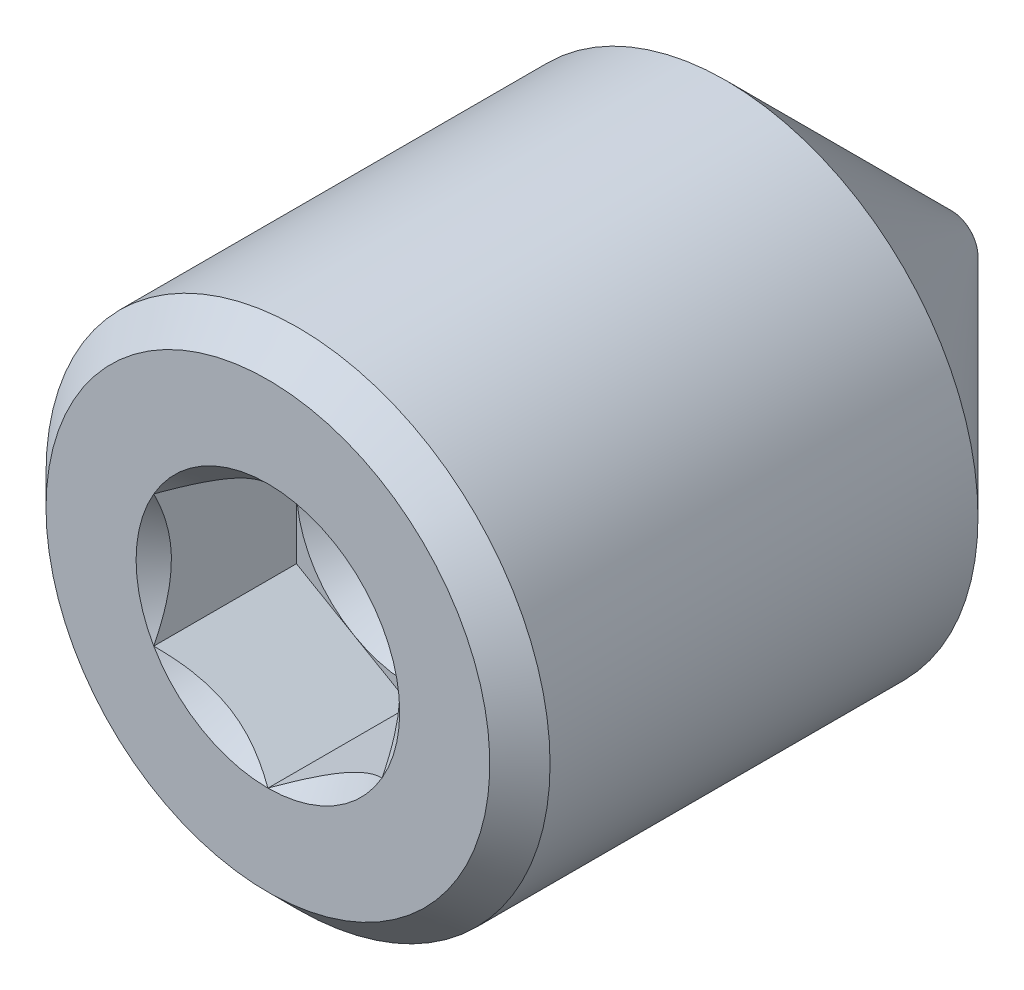
SolidWorks part; units mm, degrees
ref_plane "Front Plane" through (0, 0, 0) normal (0, 0, 1) x (1, 0, 0)
ref_plane "Top Plane" through (0, 0, 0) normal (0, 1, 0) x (1, 0, 0)
ref_plane "Right Plane" through (0, 0, 0) normal (1, 0, 0) x (0, 0, -1)
sketch "Sketch1" plane through (0, 0, 0) normal (1, 0, 0) x (0, 0, -1)
  line L0 (-2.3812, 0) -> (2.3812, 0) construction
  line L5 (-2.3812, 1.7526) -> (-2.3812, -1.7526) construction
  line L6 (2.3812, 0.1753) -> (2.3812, -0.1753) construction
  line L7 (2.3812, 0.1753) -> (0.8039, 1.7526) construction
  line L8 (2.3812, -0.1753) -> (0.8039, -1.7526) construction
  line L9 (-2.9766, 1.8213) -> (-2.3416, 1.8213) construction
  line L10 (-2.3416, 1.8213) -> (-2.6591, 1.2714) construction
  line L11 (-2.6591, 1.2714) -> (-2.9766, 1.8213) construction
  line L12 (-2.9369, 1.7526) -> (-2.3812, 1.7526) construction
  line L13 (-2.6987, 1.3402) -> (-2.6194, 1.3402) construction
  line L14 (-2.6591, 1.3402) -> (-2.6591, 1.2714) construction
  line L15 (-2.6591, 1.7526) -> (-2.6591, 1.8213) construction
  point P24 (-2.3812, 0.7938)
  point P29 (-0.7937, -1.7526)
  dimension "Screw Size Decimal Equivalent" = 3.5052
  dimension "Length" = 4.7625
  dimension "Cone Point Angle" = 90
  dimension "Drive Size" = 1.5875
  dimension "Approx. Point OD" = 0.3505
  dimension "Thread Pitch" = 0.635
  dimension "Pitch/8" = 0.0794
  dimension "Thread Note" = 1.5875
sketch "Sketch2" plane through (0, 0, 0) normal (1, 0, 0) x (0, 0, -1)
  line L0 (-2.3812, 0) -> (2.3812, 0)
  line L1 (2.3812, 0) -> (2.3812, 0.1753)
  line L2 (2.3812, 0.1753) -> (0.8039, 1.7526)
  line L3 (0.8039, 1.7526) -> (-2.3812, 1.7526)
  line L4 (-2.3812, 1.7526) -> (-2.3812, 0)
revolve "Revolve1" add sketch "Sketch2" angle 360 about L0
chamfer "Chamfer1" distance 0.2095 angle 45 1 edges at (1.7526, 0, 2.3812)
sketch "Sketch3" plane through (0, 0, 2.3812) normal (0, 0, 1) x (1, 0, 0)
  line L1 (0, -0.9165) -> (0.7938, -0.4583)
  line L2 (0.7938, -0.4583) -> (0.7938, 0.4583)
  line L3 (0.7938, 0.4583) -> (0, 0.9165)
  line L4 (0, 0.9165) -> (-0.7938, 0.4583)
  line L5 (-0.7938, 0.4583) -> (-0.7938, -0.4583)
  line L6 (-0.7938, -0.4583) -> (0, -0.9165)
  circle A0 centre (0, 0) radius 0.7938 construction
  circle A1 centre (0, 0) radius 1.7526 construction
extrude "Cut-Extrude1" cut sketch "Sketch3" against normal blind 0.9922
sketch "Sketch4" plane through (0, 0, 2.3812) normal (0, 0, 1) x (1, 0, 0)
  circle A0 centre (0, 0) radius 0.9165
extrude "Cut-Extrude2" cut sketch "Sketch4" against normal through all draft 45
sketch "Sketch5" plane through (0, 0, 1.3891) normal (0, 0, 1) x (1, 0, 0)
  line L0 (0, 0.9165) -> (0.7938, 0.4583) construction
  circle A0 centre (0, 0) radius 0.7938
extrude "Cut-Extrude3" cut sketch "Sketch5" against normal through all draft 45
fillet "Fillet1" radius 0.0351 1 edges at (0.1753, 0, -2.3812)
sketch "Sketch6" [suppressed] plane through (0, 0, 2.3812) normal (0, 0, -1) x (-1, 0, 0)
  circle A0 centre (0, 0) radius 1.7526 construction
  circle A1 centre (0, 0) radius 1.7526
sketch "Sketch10" [suppressed] plane through (0, 0, 0) normal (1, 0, 0) x (0, 0, -1)
  line L0 (0.6292, 0) -> (2.371, 0) construction
  line L1 (-2.3812, 0) -> (2.3812, 0) construction
  line L2 (2.371, 0) -> (2.371, 0.1855)
  line L3 (2.371, 0.1855) -> (0.7482, 1.7526)
  line L5 (0.7482, 1.7526) -> (0.6292, 1.7526) construction
  line L6 (0.6292, 1.7526) -> (0.6292, 0) construction
  line L7 (2.371, 0) -> (2.49, 0)
  line L8 (2.49, 0) -> (2.49, 1.7526)
  line L9 (2.49, 1.7526) -> (0.7482, 1.7526)
  dimension "D1" = 44
  dimension "D2" = 0.1191
revolve "Cut-Revolve6" [suppressed] cut sketch "Sketch10" angle 360 about L0
curve "Helix/Spiral1" [suppressed] pitch 0.635 height 5.3975 turns 8.5
sketch "Sketch7" [suppressed] plane through (0, 0, 0) normal (1, 0, 0) x (0, 0, -1)
  line L6 (-2.6987, 1.3402) -> (-2.6194, 1.3402)
  line L9 (-2.6194, 1.3402) -> (-2.3614, 1.787)
  line L10 (-2.3416, 1.8213) -> (-2.6591, 1.2714) construction
  line L11 (-2.3614, 1.787) -> (-2.9567, 1.787)
  line L12 (-2.6591, 1.2714) -> (-2.9766, 1.8213) construction
  line L13 (-2.9567, 1.787) -> (-2.6987, 1.3402)
  line L14 (-2.6591, 1.7526) -> (-2.6591, 1.8213) construction
  point P10 (-2.6591, 1.787)
sweep "Cut-Sweep1" [suppressed] cut profiles "Sketch7" path "Helix/Spiral1"
fillet "Fillet2" [suppressed] radius 0.0351
equation "\"D1@Chamfer1\"=\"Thread Pitch@Sketch1\" * .33"
equation "\"D1@Cut-Extrude1\"=\"Drive Size@Sketch1\"*.625"
equation "\"D4@Helix/Spiral1\"=\"Thread Pitch@Sketch1\""
equation "\"D3@Helix/Spiral1\"=\"Length@Sketch1\"+\"Thread Pitch@Sketch1\""
equation "\"Approx. Point OD@Sketch1\"=\"Screw Size Decimal Equivalent@Sketch1\"*.1"
equation "\"Pitch/8@Sketch1\" = \"Thread Pitch@Sketch1\" / 8"
equation "\"Thread Note@Sketch1\"=\"Thread Pitch@Sketch1\"*2.5"
equation "\"D1@Sketch10\"=(\"Cone Point Angle@Sketch1\"*.5)-1"
equation "\"D2@Sketch10\"=\"Length@Sketch1\"*.025"
equation "\"D1@Fillet1\"=\"Approx. Point OD@sketch1\"*.1"
equation "\"D1@Fillet2\"=\"d1@fillet1\""
